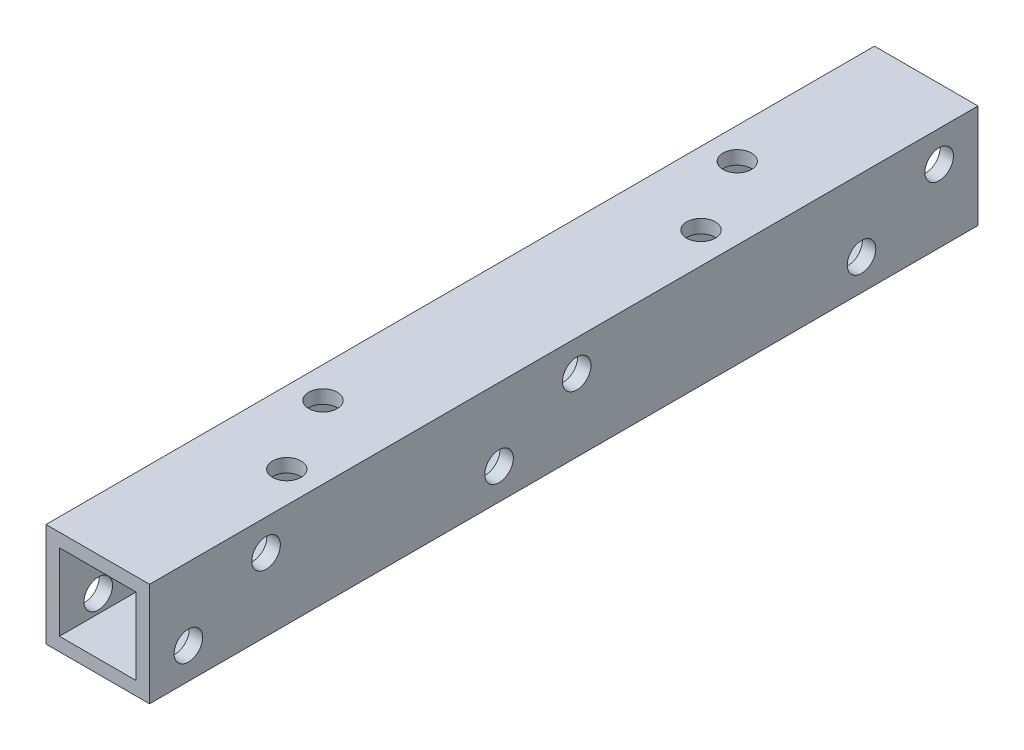
SolidWorks part; units mm, degrees
material "6061-T4 (SS)"
ref_plane "Front Plane" through (0, 0, 0) normal (1, 0, 0) x (0, 1, 0)
ref_plane "Top Plane" through (0, 0, 0) normal (0, 0, 1) x (0, 1, 0)
ref_plane "Right Plane" through (0, 0, 0) normal (0, 1, 0) x (-1, 0, 0)
sketch "Sketch1" plane through (0, 0, 0) normal (0, 0, 1) x (0, 1, 0)
  line L1 (6.35, -6.35) -> (-6.35, -6.35)
  line L2 (6.35, -6.35) -> (6.35, 6.35)
  line L3 (6.35, 6.35) -> (-6.35, 6.35)
  line L4 (-6.35, -6.35) -> (-6.35, 6.35)
  line L5 (6.35, -6.35) -> (-6.35, 6.35) construction
  line L6 (6.35, 6.35) -> (-6.35, -6.35) construction
  line L7 (4.699, -4.699) -> (-4.699, -4.699)
  line L8 (4.699, -4.699) -> (4.699, 4.699)
  line L9 (4.699, 4.699) -> (-4.699, 4.699)
  line L10 (-4.699, -4.699) -> (-4.699, 4.699)
  line L11 (4.699, -4.699) -> (-4.699, 4.699) construction
  line L12 (4.699, 4.699) -> (-4.699, -4.699) construction
  point P0 (0, 0)
  point P6 (0, 0)
  dimension "D1" = 12.7
  dimension "D2" = 1.651
extrude "Boss-Extrude1" add sketch "Sketch1" along normal blind 101.6
sketch "Sketch2" plane through (0, 6.35, 0) normal (0, 1, 0) x (-1, 0, 0)
  line L0 (-6.35, 50.8) -> (6.35, 50.8) construction
  line L1 (-6.35, 101.6) -> (-6.35, 0) construction
  line L2 (6.35, 101.6) -> (6.35, 0) construction
  line L3 (-6.35, 101.6) -> (6.35, 101.6) construction
  line L12 (2.54, 20.6375) -> (-2.54, 20.6375) construction
  line L15 (2.54, 71.4375) -> (-2.54, 71.4375) construction
  line L16 (2.54, 71.4375) -> (2.54, 80.9625) construction
  line L17 (2.54, 80.9625) -> (-2.54, 80.9625) construction
  line L18 (-2.54, 71.4375) -> (-2.54, 80.9625) construction
  line L19 (2.54, 71.4375) -> (-2.54, 80.9625) construction
  line L20 (2.54, 80.9625) -> (-2.54, 71.4375) construction
  line L21 (2.54, 20.6375) -> (2.54, 30.1625) construction
  line L22 (2.54, 30.1625) -> (-2.54, 30.1625) construction
  line L23 (-2.54, 20.6375) -> (-2.54, 30.1625) construction
  line L24 (2.54, 20.6375) -> (-2.54, 30.1625) construction
  line L25 (2.54, 30.1625) -> (-2.54, 20.6375) construction
  circle A4 centre (-2.54, 80.9625) radius 1.75
  circle A5 centre (2.54, 71.4375) radius 1.75
  circle A6 centre (-2.54, 30.1625) radius 1.75
  circle A7 centre (2.54, 20.6375) radius 1.75
  point P7 (0, 101.6)
  point P8 (0, 25.4)
  point P10 (0, 76.2)
  dimension "D2" = 25.4
  dimension "D13" = 3.5
  dimension "D3" = 5.08
  dimension "D4" = 9.525
  dimension "D5" = 25.4
  dimension "D11" = 5.08
  dimension "D12" = 9.525
extrude "Cut-Extrude1" cut sketch "Sketch2" against normal blind 22.2885
sketch "Sketch3" plane through (6.35, 0, 0) normal (1, 0, 0) x (0, 1, 0)
  line L1 (2.54, 4.7625) -> (-2.54, 4.7625) construction
  line L2 (2.54, 4.7625) -> (2.54, 14.2875) construction
  line L7 (2.54, 14.2875) -> (-2.54, 14.2875) construction
  line L11 (-2.54, 4.7625) -> (-2.54, 14.2875) construction
  line L13 (2.54, 4.7625) -> (-2.54, 14.2875) construction
  line L18 (2.54, 14.2875) -> (-2.54, 4.7625) construction
  line L20 (2.54, 87.3125) -> (-2.54, 87.3125) construction
  line L21 (2.54, 87.3125) -> (2.54, 96.8375) construction
  line L22 (2.54, 96.8375) -> (-2.54, 96.8375) construction
  line L23 (-2.54, 87.3125) -> (-2.54, 96.8375) construction
  line L24 (2.54, 87.3125) -> (-2.54, 96.8375) construction
  line L25 (2.54, 96.8375) -> (-2.54, 87.3125) construction
  line L26 (-6.35, 101.6) -> (6.35, 101.6) construction
  line L27 (2.54, 49.2125) -> (-2.54, 49.2125) construction
  line L28 (2.54, 49.2125) -> (2.54, 58.7375) construction
  line L29 (2.54, 58.7375) -> (-2.54, 58.7375) construction
  line L30 (-2.54, 49.2125) -> (-2.54, 58.7375) construction
  line L31 (2.54, 49.2125) -> (-2.54, 58.7375) construction
  line L32 (2.54, 58.7375) -> (-2.54, 49.2125) construction
  line L33 (-6.35, 0) -> (6.35, 0) construction
  circle A8 centre (-2.54, 14.2875) radius 1.75
  circle A9 centre (2.54, 4.7625) radius 1.75
  circle A10 centre (-2.54, 96.8375) radius 1.75
  circle A11 centre (2.54, 87.3125) radius 1.75
  circle A12 centre (-2.54, 58.7375) radius 1.75
  circle A13 centre (2.54, 49.2125) radius 1.75
  point P0 (0, 9.525)
  point P8 (0, 92.075)
  point P15 (0, 53.975)
  point P16 (0, 101.6)
  dimension "D4" = 3.5
  dimension "D7" = 3.5
  dimension "D11" = 3.5
  dimension "D1" = 5.08
  dimension "D2" = 9.525
  dimension "D3" = 9.525
  dimension "D5" = 5.08
  dimension "D6" = 9.525
  dimension "D8" = 9.525
  dimension "D9" = 5.08
  dimension "D10" = 9.525
  dimension "D12" = 53.975
extrude "Cut-Extrude2" cut sketch "Sketch3" against normal blind 22.098 contours A10 | A11 | A8 | A9 | A12 | A13 region at (6.35, -2.54, 14.2875) region at (6.35, 2.54, 4.7625) region at (6.35, -2.54, 96.8375) region at (6.35, 2.54, 87.3125) region at (6.35, -2.54, 58.7375) region at (6.35, 2.54, 49.2125)
